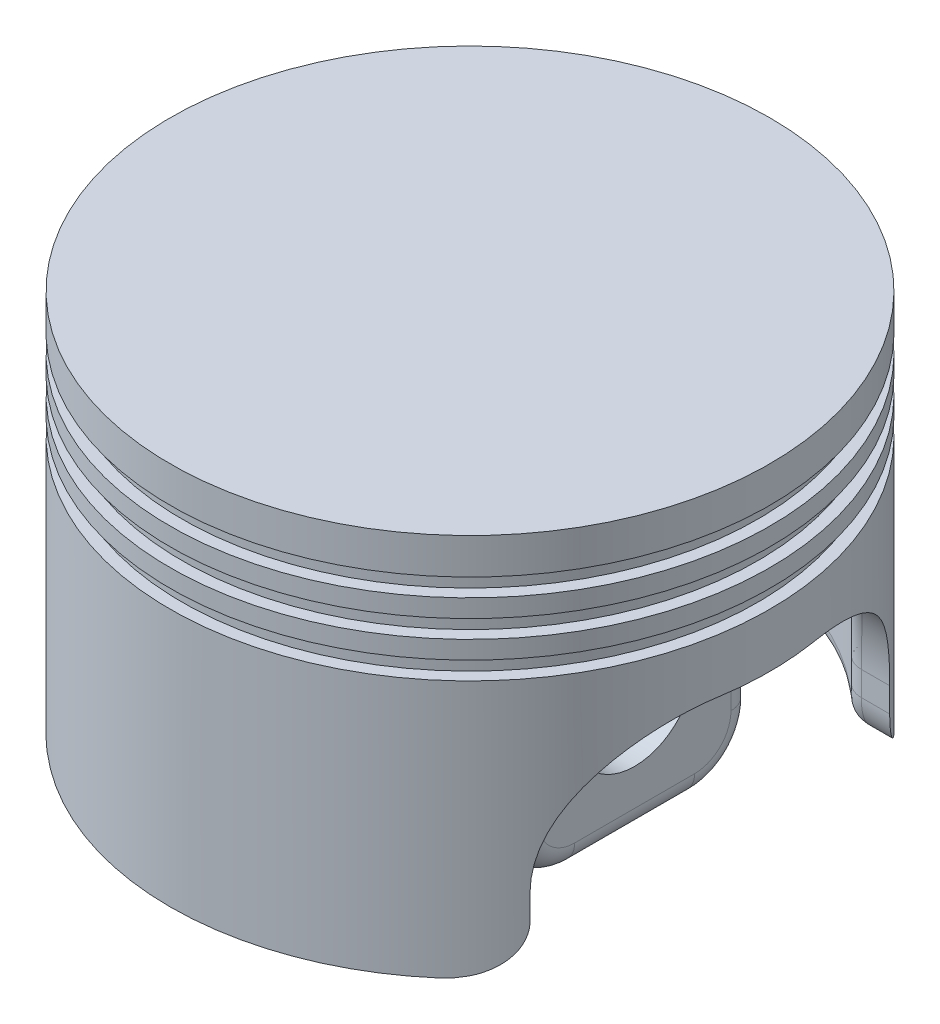
SolidWorks part; units mm, degrees
ref_plane "Front Plane" through (0, 0, 0) normal (0, 0, 1) x (1, 0, 0)
ref_plane "Top Plane" through (0, 0, 0) normal (0, 1, 0) x (1, 0, 0)
ref_plane "Right Plane" through (0, 0, 0) normal (1, 0, 0) x (0, 0, -1)
sketch "Sketch1" plane through (0, 0, 0) normal (1, 0, 0) x (0, 0, -1)
  line L0 (0, 0) -> (63.5, 0)
  line L1 (63.5, 0) -> (63.5, -81.28)
  line L2 (63.5, -81.28) -> (57.15, -81.28)
  line L3 (57.15, -81.28) -> (57.15, -19)
  line L4 (57.15, -19) -> (0, -19)
  line L5 (0, -19) -> (0, 0)
  dimension "D1" = 63.5
  dimension "D2" = 81.28
  dimension "D3" = 6.35
  dimension "D4" = 19
revolve "Revolve1" add sketch "Sketch1" angle 360 about L5
sketch "Sketch3" plane through (0, 0, 0) normal (0, 0, 1) x (1, 0, 0)
  line L0 (63.5, -7.62) -> (60.96, -7.62)
  line L1 (60.96, -7.62) -> (60.96, -11.43)
  line L2 (60.96, -11.43) -> (63.5, -11.43)
  line L3 (63.5, -11.43) -> (63.5, -7.62)
  line L4 (63.5, 0) -> (-63.5, 0) construction
  dimension "D1" = 7.62
  dimension "D2" = 3.81
  dimension "D3" = 2.54
  dimension "D4" = 63.5
ref_axis "Axis1" through (0, -85.344, 0) along (0, 1, 0)
revolve "Cut-Revolve1" cut sketch "Sketch3" angle 360 about axis through (0, -85.344, 0) along (0, 1, 0)
pattern_linear "LPattern1" count 3 spacing 7.62 along (0, -1, 0) of "Cut-Revolve1"
sketch "Sketch4" plane through (0, 0, 0) normal (1, 0, 0) x (0, 0, -1)
  line L0 (0, -85.344) -> (0, 4.064) construction
  line L1 (-38.1, -38.1) -> (38.1, -38.1)
  line L2 (-38.1, -38.1) -> (-38.1, -81.28)
  line L3 (-38.1, -81.28) -> (38.1, -81.28)
  line L4 (38.1, -38.1) -> (38.1, -81.28)
  line L5 (-38.1, -38.1) -> (38.1, -81.28) construction
  line L6 (-38.1, -81.28) -> (38.1, -38.1) construction
  line L7 (-57.15, -81.28) -> (57.15, -81.28) construction
  line L8 (63.5, 0) -> (-63.5, 0) construction
  point P0 (0, -59.69)
  dimension "D1" = 76.2
  dimension "D2" = 38.1
extrude "Cut-Extrude1" cut sketch "Sketch4" against normal mid plane 281
fillet "Fillet1" radius 28 4 edges at (46.6985, -38.1, -38.1) (46.6985, -38.1, 38.1) (-46.6985, -38.1, -38.1) (-46.6985, -38.1, 38.1)
sketch "Sketch5" plane through (0, -19, 0) normal (0, -1, 0) x (1, 0, 0)
  line L1 (-34.875, 25.4) -> (-15.875, 25.4)
  line L2 (-34.875, 25.4) -> (-34.875, -25.4)
  line L3 (-34.875, -25.4) -> (-15.875, -25.4)
  line L4 (-15.875, 25.4) -> (-15.875, -25.4)
  line L5 (-34.875, 25.4) -> (-15.875, -25.4) construction
  line L6 (-34.875, -25.4) -> (-15.875, 25.4) construction
  point P0 (-25.375, 0)
  dimension "D1" = 19
  dimension "D2" = 50.8
  dimension "D3" = 15.875
extrude "Boss-Extrude2" add sketch "Sketch5" along normal blind 63.5
mirror "Mirror1" about plane through (0, 0, 0) normal (1, 0, 0) of "Boss-Extrude2"
sketch "Sketch6" plane through (-34.875, 0, 0) normal (-1, 0, 0) x (0, 0, 1)
  line L0 (25.4, -82.5) -> (-25.4, -82.5) construction
  circle A0 centre (0, -57.1) radius 12.7
  dimension "D2" = 25.4
  dimension "D1" = 25.4
extrude "Cut-Extrude2" cut sketch "Sketch6" against normal blind 97.5
fillet "Fillet2" radius 12.7 4 edges at (25.375, -82.5, -25.4) (-25.375, -82.5, -25.4) (-25.375, -82.5, 25.4) (25.375, -82.5, 25.4)
fillet "Fillet3" radius 10 4 edges at (-46.6985, -81.28, 38.1) (-46.6985, -81.28, -38.1) (46.6985, -81.28, -38.1) (46.6985, -81.28, 38.1)
fillet "Fillet4" radius 5 20 edges at (-15.875, -44.4, -25.4) (-15.875, -78.7803, -21.6803) (-15.875, -44.4, 25.4) (-15.875, -78.7803, 21.6803) (-34.875, -44.4, 25.4) (-34.875, -78.7803, 21.6803) (-34.875, -44.4, -25.4) (-34.875, -78.7803, -21.6803) (34.875, -44.4, 25.4) (34.875, -78.7803, 21.6803) (34.875, -44.4, -25.4) (34.875, -78.7803, -21.6803) (15.875, -44.4, -25.4) (15.875, -78.7803, -21.6803) (15.875, -44.4, 25.4) (15.875, -78.7803, 21.6803) (-15.875, -82.5, 0) (-34.875, -82.5, 0) (34.875, -82.5, 0) (15.875, -82.5, 0)
fillet "Fillet5" radius 5 16 edges at (41.3657, -76.2692, 39.4335) (42.5971, -68.69, 38.1) (50.4318, -43.6881, 26.8841) (57.15, -38.1, 0) (46.055, -51.2516, -33.8387) (42.5971, -68.69, -38.1) (40.0022, -78.1316, -40.816) (0, -81.28, -57.15) (-41.3657, -76.2692, -39.4335) (-42.5971, -68.69, -38.1) (-50.4318, -43.6881, -26.8841) (-57.15, -38.1, 0) (-46.055, -51.2516, 33.8387) (-42.5971, -68.69, 38.1) (-40.0022, -78.1316, 40.816) (0, -81.28, 57.15)
scale "Scale1" scale about centroid uniform scaling yes scale factor 0.51948
